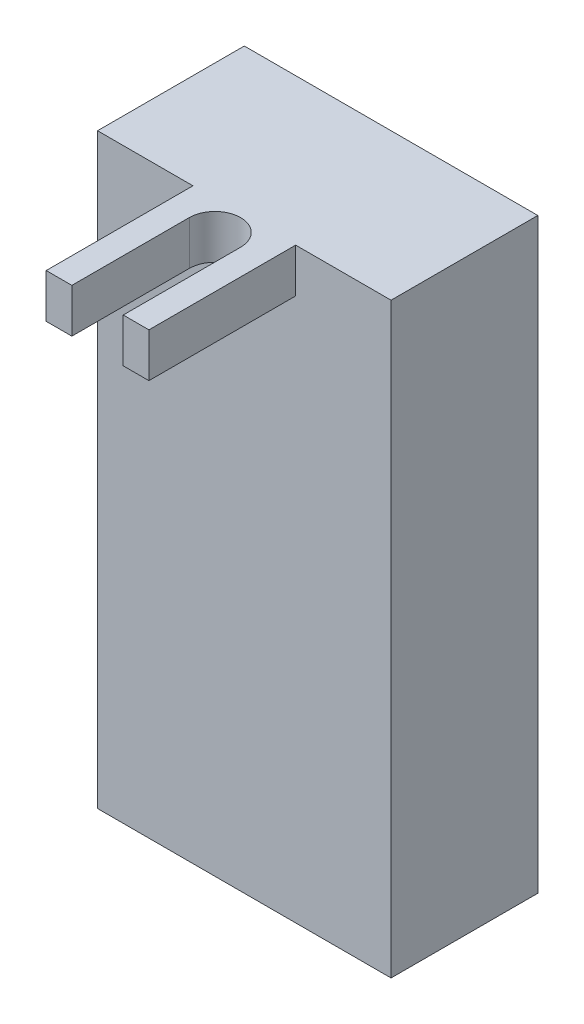
SolidWorks part; units mm, degrees
ref_plane "Front Plane" through (0, 0, 0) normal (0, 0, 1) x (1, 0, 0)
ref_plane "Top Plane" through (0, 0, 0) normal (0, 1, 0) x (1, 0, 0)
ref_plane "Right Plane" through (0, 0, 0) normal (1, 0, 0) x (0, 0, -1)
sketch "Sketch1" plane through (0, 0, 0) normal (0, 0, 1) x (1, 0, 0)
  line L1 (0, 0) -> (-20, 0)
  line L2 (0, 0) -> (0, 40)
  line L3 (0, 40) -> (-20, 40)
  line L4 (-20, 0) -> (-20, 40)
  dimension "D1" = 20
  dimension "D2" = 40
extrude "Boss-Extrude1" add sketch "Sketch1" along normal blind 10
sketch "Sketch2" plane through (0, 0, 10) normal (0, 0, 1) x (1, 0, 0)
  line L0 (0, 40) -> (-20, 40) construction
  line L1 (-13.5, 40) -> (-6.5, 40)
  line L2 (-13.5, 40) -> (-13.5, 37)
  line L3 (-13.5, 37) -> (-6.5, 37)
  line L4 (-6.5, 40) -> (-6.5, 37)
  line L6 (-10, 37) -> (-10, 40) construction
  dimension "D1" = 7
  dimension "D2" = 3
extrude "Boss-Extrude2" add sketch "Sketch2" along normal blind 10
sketch "Sketch3" plane through (0, 40, 0) normal (0, 1, 0) x (1, 0, 0)
  line L0 (-10, -20) -> (-10, -12) construction
  line L1 (-6.5, -20) -> (-13.5, -20) construction
  line L2 (-11.75, -20) -> (-11.75, -12)
  line L3 (-8.25, -20) -> (-8.25, -12)
  arc A0 (-11.75, -20) -> (-8.25, -20) centre (-10, -20) ccw
  arc A1 (-8.25, -12) -> (-11.75, -12) centre (-10, -12) ccw
  point P4 (-10, -16)
  dimension "D1" = 1.75
  dimension "D2" = 8
extrude "Cut-Extrude1" cut sketch "Sketch3" against normal blind 10
sketch "Sketch4" plane through (0, 0, 10) normal (0, 0, 1) x (1, 0, 0)
  line L0 (-20, 40) -> (-20, 0) construction
  line L1 (0, 0) -> (0, 40) construction
  point P0 (-20, 15)
  point P1 (0, 15)
  dimension "D1" = 15
